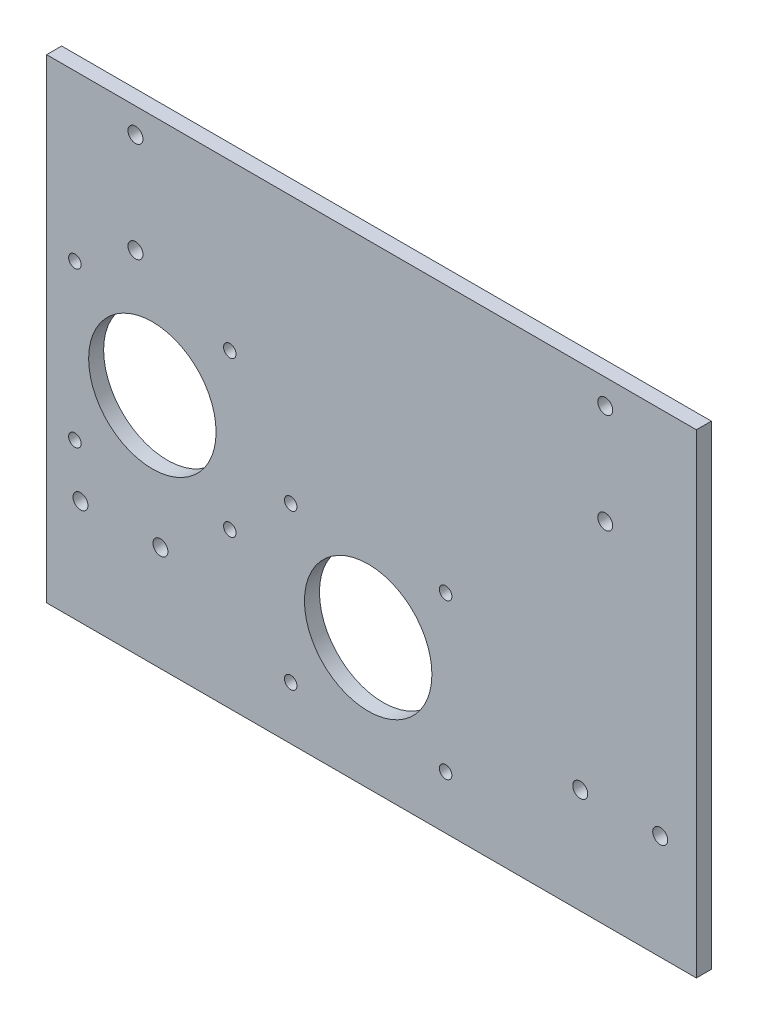
SolidWorks part; units mm, degrees
ref_plane "前视基准面" through (0, 0, 0) normal (0, 0, 1) x (1, 0, 0)
ref_plane "上视基准面" through (0, 0, 0) normal (0, 1, 0) x (1, 0, 0)
ref_plane "右视基准面" through (0, 0, 0) normal (1, 0, 0) x (0, 0, -1)
sketch "草图1" plane through (0, 0, 0) normal (0, 0, 1) x (1, 0, 0)
  line L1 (65, -47.5) -> (-65, -47.5)
  line L2 (65, -47.5) -> (65, 47.5)
  line L3 (65, 47.5) -> (-65, 47.5)
  line L4 (-65, -47.5) -> (-65, 47.5)
  line L5 (65, -47.5) -> (-65, 47.5) construction
  line L6 (65, 47.5) -> (-65, -47.5) construction
  point P0 (0, 0)
  dimension "D1" = 130
  dimension "D2" = 95
extrude "凸台-拉伸1" add sketch "草图1" along normal blind 3
sketch "草图2" plane through (0, 0, 3) normal (0, 0, 1) x (1, 0, 0)
  line L0 (0, -47.5) -> (0, -26.5) construction
  line L1 (-65, -47.5) -> (65, -47.5) construction
  line L2 (0, -26.5) -> (10, -26.5) construction
  circle A0 centre (10, -26.5) radius 1.5
  circle A1 centre (-10, -26.5) radius 1.5
  dimension "D3" = 3
  dimension "D1" = 21
  dimension "D2" = 10
sketch "草图3" plane through (0, 0, 0) normal (0, 0, -1) x (-1, 0, 0)
  circle A0 centre (-57.7671, -26.5) radius 1.5
  circle A1 centre (-41.7671, -26.5) radius 1.5
  circle A2 centre (42.2329, -26.5) radius 1.5
  circle A4 centre (58.2329, -26.5) radius 1.5
extrude "切除-拉伸2" cut sketch "草图3" against normal blind 10
sketch "草图4" plane through (0, 0, 0) normal (0, 0, -1) x (-1, 0, 0)
  circle A0 centre (-46.7671, 42.5) radius 1.5
  circle A1 centre (-46.7671, 22.5) radius 1.5
  circle A2 centre (47.2329, 42.5) radius 1.5
  circle A3 centre (47.2329, 22.5) radius 1.5
extrude "切除-拉伸3" cut sketch "草图4" against normal blind 10
sketch "草图6" plane through (0, 0, 0) normal (0, 0, -1) x (-1, 0, 0)
  circle A0 centre (0.6675, -21.35) radius 12.75
  circle A1 centre (43.85, -0.9579) radius 12.75
  dimension "D1" = 25.5
  dimension "D2" = 25.5
extrude "切除-拉伸4" cut sketch "草图6" against normal blind 10
sketch "草图7" plane through (0, 0, 3) normal (0, 0, 1) x (1, 0, 0)
  circle A0 centre (-59.35, 14.5421) radius 1.25
  circle A1 centre (-28.35, 14.5421) radius 1.25
  circle A2 centre (-59.35, -16.4579) radius 1.25
  circle A3 centre (-28.35, -16.4579) radius 1.25
  circle A4 centre (-16.1675, -5.85) radius 1.25
  circle A5 centre (14.8325, -5.85) radius 1.25
  circle A6 centre (14.8325, -36.85) radius 1.25
  circle A7 centre (-16.1675, -36.85) radius 1.25
  point P19 (-0.6675, -21.35)
  dimension "D1" = 4
extrude "切除-拉伸5" cut sketch "草图7" against normal blind 10
